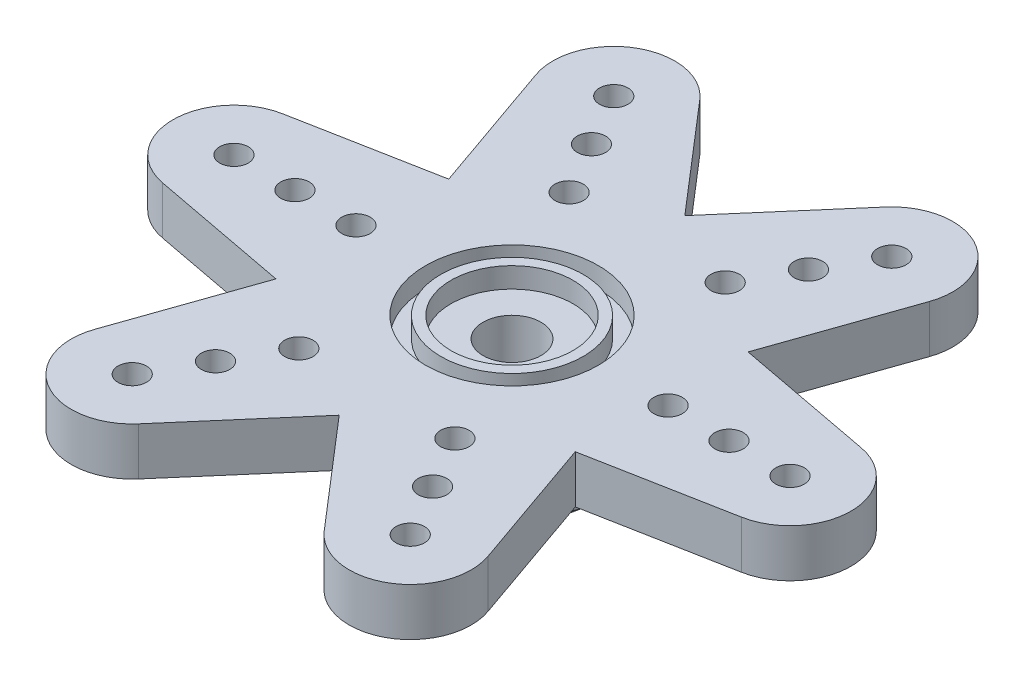
SolidWorks part; units mm, degrees
ref_plane "前视基准面" through (0, 0, 0) normal (0, 0, 1) x (1, 0, 0)
ref_plane "上视基准面" through (0, 0, 0) normal (0, 1, 0) x (1, 0, 0)
ref_plane "右视基准面" through (0, 0, 0) normal (1, 0, 0) x (0, 0, -1)
sketch "草图1" plane through (0, 0, 0) normal (0, 1, 0) x (1, 0, 0)
  line L0 (-143.9777, 0) -> (7054.9085, 0) construction
  line L1 (0, -143.9777) -> (0, 7054.9085) construction
  line L2 (-7.3612, -4.25) -> (-14.2336, -2.9475)
  line L3 (0, -8.5) -> (-4.5642, -13.8004)
  line L4 (0, -8.5) -> (4.5642, -13.8004)
  line L5 (-7.3612, -4.25) -> (-9.6694, -10.8529)
  line L6 (-7.3612, 4.25) -> (-9.6694, 10.8529)
  line L7 (-7.3612, 4.25) -> (-14.2336, 2.9475)
  line L8 (0, 8.5) -> (4.5642, 13.8004)
  line L9 (0, 8.5) -> (-4.5642, 13.8004)
  line L10 (7.3612, 4.25) -> (14.2336, 2.9475)
  line L11 (7.3612, 4.25) -> (9.6694, 10.8529)
  line L12 (7.3612, -4.25) -> (9.6694, -10.8529)
  line L13 (7.3612, -4.25) -> (14.2336, -2.9475)
  circle A0 centre (-13.675, 0) radius 0.7
  circle A1 centre (-10.675, 0) radius 0.7
  circle A2 centre (-7.675, 0) radius 0.7
  circle A4 centre (0, 0) radius 13.675 construction
  circle A5 centre (0, 0) radius 8.5 construction
  arc A6 (-4.5642, 13.8004) -> (-9.6694, 10.8529) centre (-6.8375, 11.8429) ccw
  arc A7 (9.6694, 10.8529) -> (4.5642, 13.8004) centre (6.8375, 11.8429) ccw
  arc A8 (14.2336, -2.9475) -> (14.2336, 2.9475) centre (13.675, 0) ccw
  arc A9 (4.5642, -13.8004) -> (9.6694, -10.8529) centre (6.8375, -11.8429) ccw
  arc A10 (-9.6694, -10.8529) -> (-4.5642, -13.8004) centre (-6.8375, -11.8429) ccw
  arc A11 (-14.2336, 2.9475) -> (-14.2336, -2.9475) centre (-13.675, 0) ccw
  circle A12 centre (-6.8375, 11.8429) radius 0.7
  circle A13 centre (-5.3375, 9.2448) radius 0.7
  circle A14 centre (-3.8375, 6.6467) radius 0.7
  circle A15 centre (6.8375, 11.8429) radius 0.7
  circle A16 centre (5.3375, 9.2448) radius 0.7
  circle A17 centre (3.8375, 6.6467) radius 0.7
  circle A18 centre (13.675, 0) radius 0.7
  circle A19 centre (10.675, 0) radius 0.7
  circle A20 centre (7.675, 0) radius 0.7
  circle A21 centre (6.8375, -11.8429) radius 0.7
  circle A22 centre (5.3375, -9.2448) radius 0.7
  circle A23 centre (3.8375, -6.6467) radius 0.7
  circle A24 centre (-6.8375, -11.8429) radius 0.7
  circle A25 centre (-5.3375, -9.2448) radius 0.7
  circle A26 centre (-3.8375, -6.6467) radius 0.7
  point P29 (0, 0)
  point P46 (0, 0)
  point P71 (0, 0)
  dimension "D2" = 1.4
  dimension "D1" = 6
  dimension "D3" = 3
  dimension "D4" = 3
extrude "凸台-拉伸1" add sketch "草图1" along normal blind 2.35
sketch "草图2" plane through (0, 0, 0) normal (0, -1, 0) x (1, 0, 0)
  line L0 (-1000, 0) -> (49000, 0) construction
  line L1 (0, -1000) -> (0, 49000) construction
  circle A0 centre (0, 0) radius 1.425
  circle A1 centre (0, 0) radius 4.4
  dimension "D1" = 8.8
  dimension "D2" = 2.85
extrude "凸台-拉伸2" add sketch "草图2" along normal blind 3.5
sketch "草图3" plane through (0, 0, 0) normal (0, -1, 0) x (1, 0, 0)
  circle A0 centre (0, 0) radius 1.425
  dimension "D1" = 2.85
extrude "切除-拉伸1" cut sketch "草图3" against normal through all
sketch "草图4" plane through (0, 2.35, 0) normal (0, 1, 0) x (1, 0, 0)
  line L0 (-1000, 0) -> (49000, 0) construction
  line L1 (0, -1000) -> (0, 49000) construction
  circle A0 centre (0, 0) radius 4.25
  circle A1 centre (0, 0) radius 3.5
  circle A2 centre (0, 0) radius 3
  circle A3 centre (0, 0) radius 1.425
  circle M1 centre (0, 0) radius 1.425
  dimension "D1" = 8.5
  dimension "D2" = 7
  dimension "D3" = 6
extrude "切除-拉伸2" cut sketch "草图4" against normal blind 1 contours A2 M1 region at (-2.9151, 2.35, 0)
extrude "切除-拉伸3" cut sketch "草图4<3>" against normal blind 1 contours A0 A1 region at (-4.1298, 2.35, 0)
sketch "草图4<3>" plane through (0, 2.35, 0) normal (0, 1, 0) x (1, 0, 0) same geometry as "草图4"
chamfer "倒角1" distance 0.25 angle 45 1 edges at (0, -3.5, -4.4)
